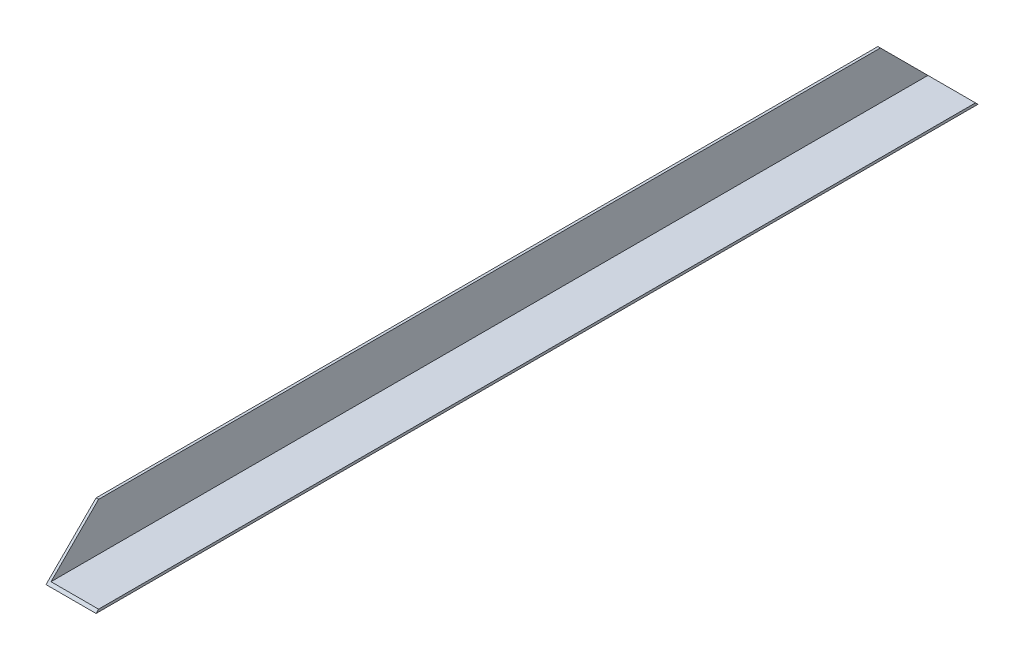
SolidWorks part; units mm, degrees
material "PC High Viscosity"
ref_plane "Front Plane" through (0, 0, 0) normal (0, 0, 1) x (1, 0, 0)
ref_plane "Top Plane" through (0, 0, 0) normal (0, 1, 0) x (1, 0, 0)
ref_plane "Right Plane" through (0, 0, 0) normal (1, 0, 0) x (0, 0, -1)
sketch "Sketch1" plane through (0, 0, 0) normal (0, 0, 1) x (1, 0, 0)
  line L0 (0, 25.4) -> (0, 0)
  line L1 (0, 0) -> (25.4, 0)
  line L2 (25.4, 0) -> (25.4, 1.27)
  line L3 (25.4, 1.27) -> (1.27, 1.27)
  line L4 (1.27, 1.27) -> (1.27, 25.4)
  line L5 (1.27, 25.4) -> (0, 25.4)
  dimension "D1" = 25.4
  dimension "D2" = 1.27
  dimension "D3" = 25.4
extrude "Boss-Extrude1" add sketch "Sketch1" along normal blind 304.8 and the other way blind 304.8
sketch "Sketch2" plane through (0, 0, 0) normal (-1, 0, 0) x (0, 0, 1)
  line L0 (223.77, 0) -> (198.37, 25.4)
  line L1 (198.37, 25.4) -> (304.8, 25.4)
  line L2 (304.8, 25.4) -> (304.8, 0)
  line L3 (304.8, 0) -> (223.77, 0)
  line L4 (0, 0) -> (0, 80.5451) construction
  line L5 (-304.8, 0) -> (304.8, 0) construction
  line L6 (-304.8, 0) -> (-304.8, 25.4)
  line L7 (-304.8, 25.4) -> (-198.37, 25.4)
  line L8 (-198.37, 25.4) -> (-223.77, 0)
  line L9 (-223.77, 0) -> (-304.8, 0)
  line L10 (304.8, 25.4) -> (304.8, 0) construction
  line L11 (-304.8, 25.4) -> (304.8, 25.4) construction
  line L12 (-304.8, 25.4) -> (-304.8, 0) construction
  line L13 (222.5, 1.27) -> (222.5, 25.4) construction
  line L15 (-222.5, 1.27) -> (-222.5, 25.4) construction
  line L16 (-304.8, 1.27) -> (304.8, 1.27) construction
  dimension "D1" = 45
  dimension "D2" = 445
extrude "Cut-Extrude1" cut sketch "Sketch2" against normal through all
